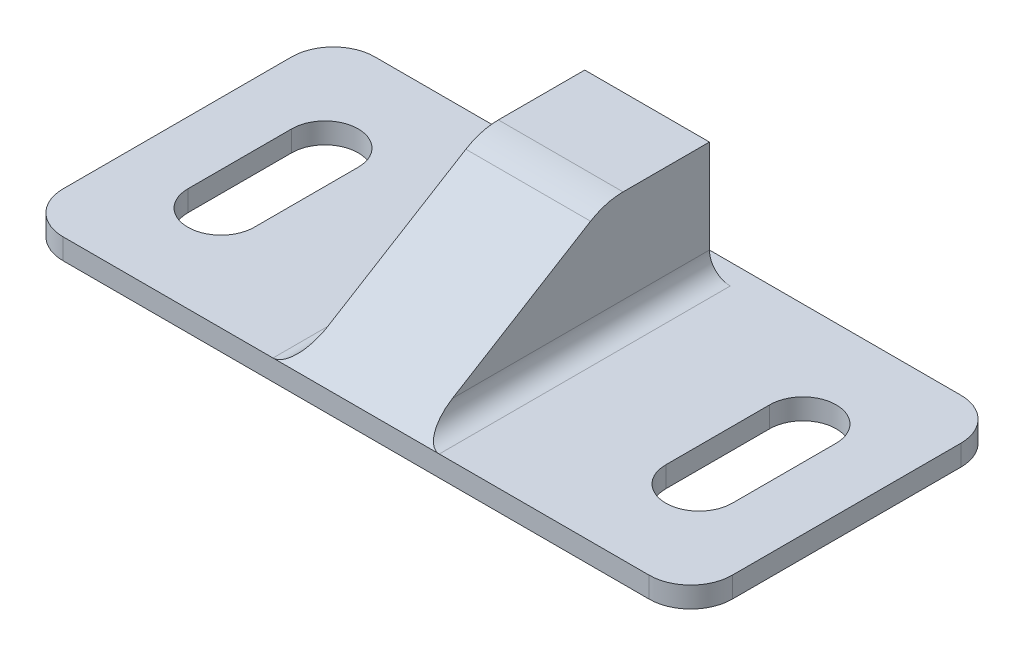
SolidWorks part; units mm, degrees
ref_plane "Front Plane" through (0, 0, 0) normal (0, 0, 1) x (1, 0, 0)
ref_plane "Top Plane" through (0, 0, 0) normal (0, 1, 0) x (1, 0, 0)
ref_plane "Right Plane" through (0, 0, 0) normal (1, 0, 0) x (0, 0, -1)
sketch "Sketch1" plane through (0, 0, 0) normal (0, 1, 0) x (1, 0, 0)
  line L0 (0, 0) -> (0, 7.5) construction
  line L1 (-14.1, -7.5) -> (14.1, -7.5)
  line L2 (-16.1, -5.5) -> (-16.1, 5.5)
  line L3 (-14.1, 7.5) -> (14.1, 7.5)
  line L4 (16.1, -5.5) -> (16.1, 5.5)
  line L5 (-16.1, -7.5) -> (16.1, 7.5) construction
  line L6 (-16.1, 7.5) -> (16.1, -7.5) construction
  line L7 (11.5, -2.5) -> (11.5, 2.5) construction
  line L8 (9.9, -2.5) -> (9.9, 2.5)
  line L9 (13.1, -2.5) -> (13.1, 2.5)
  line L10 (-11.5, -2.5) -> (-11.5, 2.5) construction
  line L11 (-9.9, -2.5) -> (-9.9, 2.5)
  line L12 (-13.1, -2.5) -> (-13.1, 2.5)
  arc A3 (-16.1, 5.5) -> (-14.1, 7.5) centre (-14.1, 5.5) cw
  arc A4 (-14.1, -7.5) -> (-16.1, -5.5) centre (-14.1, -5.5) cw
  arc A5 (14.1, -7.5) -> (16.1, -5.5) centre (14.1, -5.5) ccw
  arc A6 (14.1, 7.5) -> (16.1, 5.5) centre (14.1, 5.5) cw
  arc A7 (9.9, -2.5) -> (13.1, -2.5) centre (11.5, -2.5) ccw
  arc A8 (13.1, 2.5) -> (9.9, 2.5) centre (11.5, 2.5) ccw
  arc A9 (-9.9, -2.5) -> (-13.1, -2.5) centre (-11.5, -2.5) cw
  arc A10 (-13.1, 2.5) -> (-9.9, 2.5) centre (-11.5, 2.5) cw
  point P0 (0, 0)
  point P8 (11.5, 0)
  point P27 (0, 0)
  point P28 (13.1404, 2.5)
  point P31 (-11.5, 0)
  dimension "D2" = 3.2
  dimension "D5" = 2
  dimension "D1" = 15
  dimension "D3" = 3
  dimension "D4" = 5
  dimension "D6" = 11.5
extrude "Boss-Extrude1" add sketch "Sketch1" along normal blind 1
sketch "Sketch2" plane through (0, 0, 0) normal (1, 0, 0) x (0, 0, -1)
  line L1 (6.5, 6.5) -> (6.5, 1)
  line L2 (-7.5, 1) -> (6.5, 1)
  line L3 (6.5, 6.5) -> (2.3441, 6.5)
  line L4 (0.7797, 6.0598) -> (-7.5, 1)
  arc A0 (2.3441, 6.5) -> (0.7797, 6.0598) centre (2.3441, 3.5) ccw
  point P5 (0, 0)
  point P9 (1.5, 6.5)
  dimension "D3" = 3
  dimension "D1" = 5.5
  dimension "D2" = 5
  dimension "D4" = 14
extrude "Boss-Extrude2" add sketch "Sketch2" along normal blind 3 and the other way blind 3
fillet "Fillet1" radius 1 2 edges at (-3, 1, 0.5) (3, 1, 0.5)
